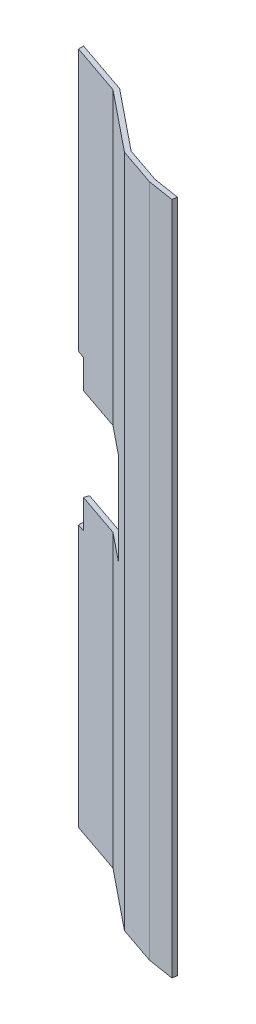
SolidWorks part; units mm, degrees
material "Alum Plate"
ref_plane "Front Plane" through (0, 0, 0) normal (0, 0, 1) x (1, 0, 0)
ref_plane "Top Plane" through (0, 0, 0) normal (0, 1, 0) x (1, 0, 0)
ref_plane "Right Plane" through (0, 0, 0) normal (1, 0, 0) x (0, 0, -1)
sketch "Sketch1" plane through (0, 0, 0) normal (0, 1, 0) x (1, 0, 0)
  line B0 (-37.0626, 23.5832) -> (-37.0626, 21.9048)
  line B1 (-18.9754, 17.3756) -> (-37.0626, 23.5832)
  line B2 (21.3237, -5.6863) -> (21.5743, -4.0939)
  line B3 (12.7923, -2.712) -> (21.5743, -4.0939)
  line B4 (-18.9754, 17.3756) -> (0.7801, 1.4107)
  line B5 (0.7801, 1.4107) -> (12.7923, -2.712)
  line B6 (21.3237, -5.6863) -> (12.5417, -4.3044)
  line B7 (12.5417, -4.3044) -> (0, 0)
  line B8 (0, 0) -> (-19.7555, 15.9649)
  line B9 (-19.7555, 15.9649) -> (-37.0626, 21.9048)
  line B10 (-37.0626, 21.9048) -> (-37.0626, 23.5832)
sketch_block_instance "Wedge sketch block-1"
sketch_block "Wedge sketch block" parameters "D1"=160, "D2"=25.4, "D3"=170, "D4"=1.5875, "D5"=1.5875, "D6"=1.5875, "D7"=160, "D8"=8.89, "D9"=8.89, "D10"=12.7
sketch "Sketch3" plane through (0, 0, 0) normal (0, 1, 0) x (1, 0, 0)
  line L0 (-37.0626, 21.9048) -> (-19.7555, 15.9649)
  line L1 (-19.7555, 15.9649) -> (0, 0)
  line L2 (0, 0) -> (12.5417, -4.3044)
  line L3 (12.5417, -4.3044) -> (21.3237, -5.6863)
  line L4 (21.3237, -5.6863) -> (21.5743, -4.0939)
  line L5 (21.5743, -4.0939) -> (12.7923, -2.712)
  line L6 (12.7923, -2.712) -> (0.7801, 1.4107)
  line L7 (0.7801, 1.4107) -> (-18.9754, 17.3756)
  line L8 (-18.9754, 17.3756) -> (-37.0626, 23.5832)
  line L9 (-37.0626, 23.5832) -> (-37.0626, 21.9048)
  dimension "D1" = 160
  dimension "D2" = 25.4
  dimension "D3" = 1.5875
  dimension "D4" = 1.5875
  dimension "D5" = 19.1227
extrude "Boss-Extrude2" add sketch "Sketch3" along normal blind 222.25
sketch "Sketch4" plane through (3.3354, 0, -9.7184) normal (0.3246, 0, -0.9458) x (-0.9458, 0, -0.3246)
  line L0 (42.711, 222.25) -> (42.711, 0) construction
  line L1 (42.711, 126.365) -> (12.231, 126.365)
  line L2 (42.711, 126.365) -> (42.711, 95.885)
  line L3 (42.711, 95.885) -> (12.231, 95.885)
  line L4 (12.231, 126.365) -> (12.231, 95.885)
  line L6 (-0.2799, 222.25) -> (23.5883, 222.25) construction
  line L7 (23.5883, 0) -> (42.711, 0) construction
  line L9 (42.711, 126.365) -> (39.536, 126.365)
  line L10 (42.711, 126.365) -> (42.711, 135.89)
  line L11 (42.711, 135.89) -> (39.536, 135.89)
  line L12 (39.536, 126.365) -> (39.536, 135.89)
  line L13 (42.711, 95.885) -> (39.536, 95.885)
  line L14 (42.711, 95.885) -> (42.711, 86.36)
  line L15 (42.711, 86.36) -> (39.536, 86.36)
  line L16 (39.536, 95.885) -> (39.536, 86.36)
  line M6 (42.711, 0) -> (42.711, 222.25)
  line M8 (23.5883, 222.25) -> (23.5883, 0)
  dimension "D1" = 95.885
  dimension "D2" = 95.885
  dimension "D3" = 30.48
  dimension "D4" = 3.175
  dimension "D5" = 3.175
  dimension "D6" = 9.525
  dimension "D7" = 9.525
extrude "Cut-Extrude2" cut sketch "Sketch4" against normal through all both and the other way through all contours L12 L1 L11 M6 | L3 L1 M6 M8 | L3 L16 L15 M6 | L1 L4 L3 M8 region at (-28.019, 111.125, -20.4794) region at (-35.561, 131.1275, -23.0678) region at (-35.561, 91.1225, -23.0678) region at (-13.6043, 111.125, -15.5322)
